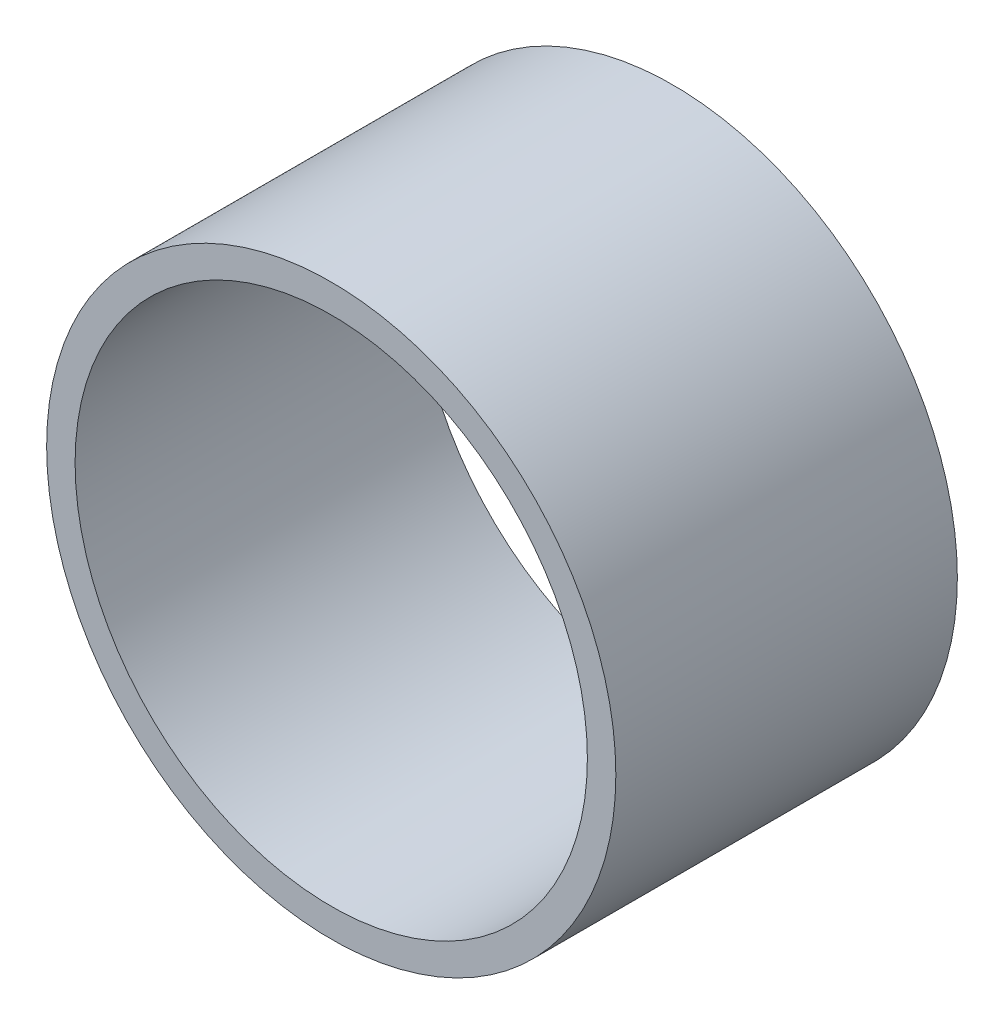
SolidWorks part; units mm, degrees
ref_plane "Plan de face" through (0, 0, 0) normal (0, 0, 1) x (1, 0, 0)
ref_plane "Plan de dessus" through (0, 0, 0) normal (0, 1, 0) x (1, 0, 0)
ref_plane "Plan de droite" through (0, 0, 0) normal (1, 0, 0) x (0, 0, -1)
sketch "Esquisse1" plane through (0, 0, 0) normal (0, 0, 1) x (1, 0, 0)
  circle A0 centre (0, 0) radius 10
  circle A1 centre (0, 0) radius 9
  dimension "D1" = 20
  dimension "D2" = 18
extrude "Boss.-Extru.1" add sketch "Esquisse1" along normal blind 12
equation "\"è.2\"=14.4"
